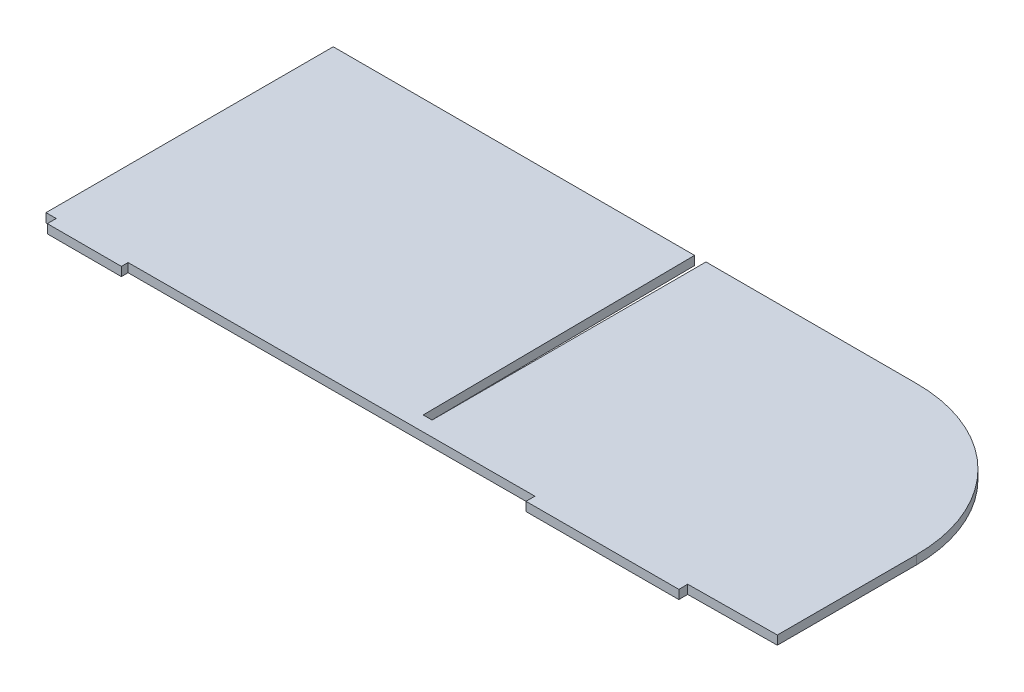
SolidWorks part; units mm, degrees
material "Maple"
ref_plane "Front Plane" through (0, 0, 0) normal (0, 0, 1) x (1, 0, 0)
ref_plane "Top Plane" through (0, 0, 0) normal (0, 1, 0) x (1, 0, 0)
ref_plane "Right Plane" through (0, 0, 0) normal (1, 0, 0) x (0, 0, -1)
sketch "Sketch1" plane through (0, 0, 0) normal (0, 1, 0) x (1, 0, 0)
  line L1 (-230.9393, 359.6133) -> (13.0607, 359.6133)
  line L2 (-230.9393, 359.6133) -> (-230.9393, 165.6133)
  line L3 (-230.9393, 165.6133) -> (-224.0414, 165.6133)
  line L7 (14.7729, 174.6174) -> (20.7729, 174.6326)
  line L8 (14.7729, 174.6174) -> (13.0607, 359.6133)
  line L13 (263.0607, 259.6133) -> (263.0607, 165.5254)
  line L18 (20.7729, 174.6326) -> (20.7729, 359.6133)
  line L19 (203.1172, 158.9599) -> (100.0154, 158.8332)
  line L21 (-224.0414, 165.6133) -> (-224.0414, 159.6133)
  line L22 (-224.0414, 159.6133) -> (-174.0414, 159.6133)
  line L23 (-174.0414, 164.1391) -> (-174.0414, 159.6133)
  line L24 (203.0607, 164.9596) -> (263.0607, 165.5254)
  line L25 (163.0607, 359.6133) -> (20.7729, 359.6133)
  line L26 (100.0002, 164.8332) -> (100.0154, 158.8332)
  line L28 (203.0607, 164.9596) -> (203.1172, 158.9599)
  line L31 (100.0002, 164.8332) -> (-174.0414, 164.1391)
  arc A0 (263.0607, 259.6133) -> (163.0607, 359.6133) centre (163.0607, 259.6133) ccw
  point P0 (0, 0)
  dimension "D3" = 100
  dimension "D2" = 194
  dimension "D4" = 50
  dimension "D6" = 494
  dimension "D7" = 6
  dimension "D8" = 6
  dimension "D9" = 244
  dimension "D10" = 6
  dimension "D13" = 6
extrude "Boss-Extrude1" add sketch "Sketch1" along normal blind 6
